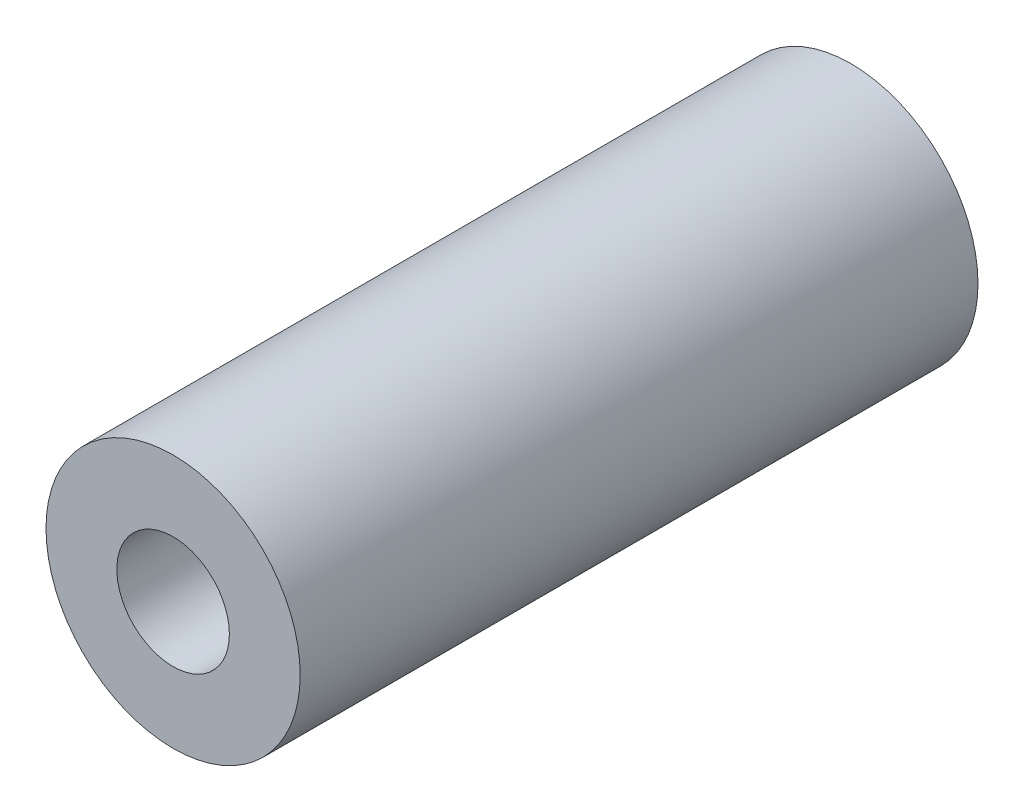
SolidWorks part; units mm, degrees
ref_plane "Front Plane" through (0, 0, 0) normal (0, 0, 1) x (1, 0, 0)
ref_plane "Top Plane" through (0, 0, 0) normal (0, 1, 0) x (1, 0, 0)
ref_plane "Right Plane" through (0, 0, 0) normal (1, 0, 0) x (0, 0, -1)
sketch "Sketch1" plane through (0, 0, 0) normal (0, 0, 1) x (1, 0, 0)
  circle A0 centre (0, 0) radius 4.7625
  circle A1 centre (0, 0) radius 2.1082
  dimension "OD" = 9.525
  dimension "ID" = 4.2164
extrude "Extrude1" add sketch "Sketch1" along normal mid plane 25.4
sketch "Sketch2" plane through (0, 0, 0) normal (1, 0, 0) x (0, 0, -1)
  line L0 (-12.7, -2.1082) -> (12.7, -2.1082) construction
  line L3 (12.7, 2.1082) -> (-12.7, 2.1082) construction
  line L5 (-12.7, -2.1082) -> (12.7, -2.1082)
  line L6 (12.7, 2.1082) -> (-12.7, 2.1082)
sketch "Sketch4" plane through (0, 0, 12.7) normal (0, 0, 1) x (1, 0, 0)
  line L0 (0, 0) -> (-1.4907, 1.4907)
  line L1 (0, -5.2388) -> (0, 5.2388) construction
  circle A0 centre (0, 0) radius 2.1082 construction
  dimension "D1" = 45
